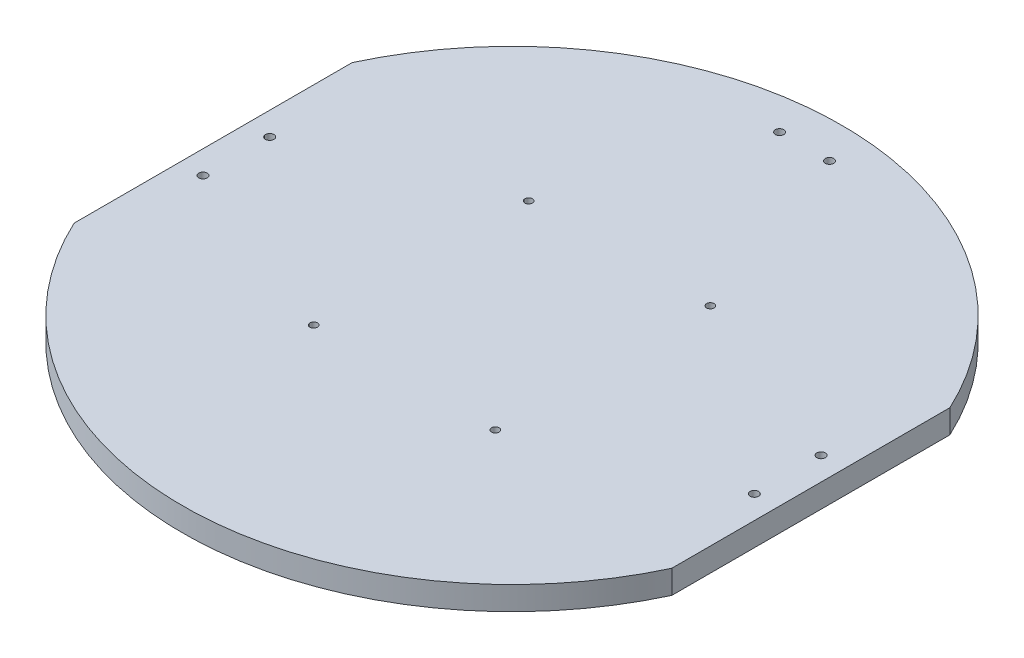
SolidWorks part; units mm, degrees
ref_plane "Front Plane" through (0, 0, 0) normal (0, 0, 1) x (1, 0, 0)
ref_plane "Top Plane" through (0, 0, 0) normal (0, 1, 0) x (1, 0, 0)
ref_plane "Right Plane" through (0, 0, 0) normal (1, 0, 0) x (0, 0, -1)
sketch "Sketch1" plane through (0, 0, 0) normal (0, 1, 0) x (1, 0, 0)
  line L0 (-80.6037, 37.5) -> (-80.6037, -37.5)
  line L1 (0, -88.9) -> (0, 88.9) construction
  line L2 (80.6037, 37.5) -> (80.6037, -37.5)
  arc A0 (-80.6037, -37.5) -> (80.6037, -37.5) centre (0, 0) ccw
  arc A1 (80.6037, 37.5) -> (-80.6037, 37.5) centre (0, 0) ccw
  dimension "D1" = 177.8
  dimension "D2" = 75
extrude "Main Body" add sketch "Sketch1" along normal blind 6.35
sketch "Sketch2" plane through (0, 6.35, 0) normal (0, 1, 0) x (1, 0, 0)
  line L1 (24.5, 29) -> (-24.5, 29) construction
  line L2 (24.5, 29) -> (24.5, -29) construction
  line L3 (24.5, -29) -> (-24.5, -29) construction
  line L4 (-24.5, 29) -> (-24.5, -29) construction
  line L5 (24.5, 29) -> (-24.5, -29) construction
  line L6 (24.5, -29) -> (-24.5, 29) construction
  circle A0 centre (24.5, 29) radius 1.025
  circle A1 centre (24.5, -29) radius 1.025
  circle A2 centre (-24.5, -29) radius 1.025
  circle A3 centre (-24.5, 29) radius 1.025
  point P0 (0, 0)
  dimension "D3" = 2.05
  dimension "D1" = 49
  dimension "D2" = 58
extrude "Raspberry Pi" cut sketch "Sketch2" against normal up to next
sketch "Sketch3" plane through (0, 6.35, 0) normal (0, 1, 0) x (1, 0, 0)
  line L0 (-80.6037, 0) -> (80.6037, 0) construction
  line L1 (-80.6037, 37.5) -> (-80.6037, -37.5) construction
  line L2 (80.6037, -37.5) -> (80.6037, 37.5) construction
  line L3 (-74.3537, -9) -> (-74.3537, 9) construction
  line L4 (0, -88.9) -> (0, 88.9) construction
  line L5 (74.3537, -9) -> (74.3537, 9) construction
  circle A0 centre (-74.3537, 9) radius 1.143
  circle A1 centre (-74.3537, -9) radius 1.143
  arc A2 (-80.6037, -37.5) -> (80.6037, -37.5) centre (0, 0) ccw construction
  arc A3 (80.6037, 37.5) -> (-80.6037, 37.5) centre (0, 0) ccw construction
  circle A4 centre (74.3537, 9) radius 1.143
  circle A5 centre (74.3537, -9) radius 1.143
  point P10 (-74.3537, 0)
  point P19 (74.3537, 0)
  dimension "D1" = 6.25
  dimension "D2" = 2.286
  dimension "D3" = 18
extrude "Motor Mounts" cut sketch "Sketch3" against normal up to next
sketch "Sketch4" plane through (0, 6.35, 0) normal (0, 1, 0) x (1, 0, 0)
  line L0 (0, -88.9) -> (0, 88.9) construction
  line L1 (-6.731, 78.9) -> (6.731, 78.9) construction
  arc A0 (-80.6037, -37.5) -> (80.6037, -37.5) centre (0, 0) ccw construction
  arc A1 (80.6037, 37.5) -> (-80.6037, 37.5) centre (0, 0) ccw construction
  circle A2 centre (-6.731, 78.9) radius 1.143
  circle A3 centre (6.731, 78.9) radius 1.143
  point P10 (0, 78.9)
  dimension "D1" = 2.286
  dimension "D2" = 13.462
  dimension "D3" = 10
extrude "Cut-Extrude3" cut sketch "Sketch4" against normal up to next
